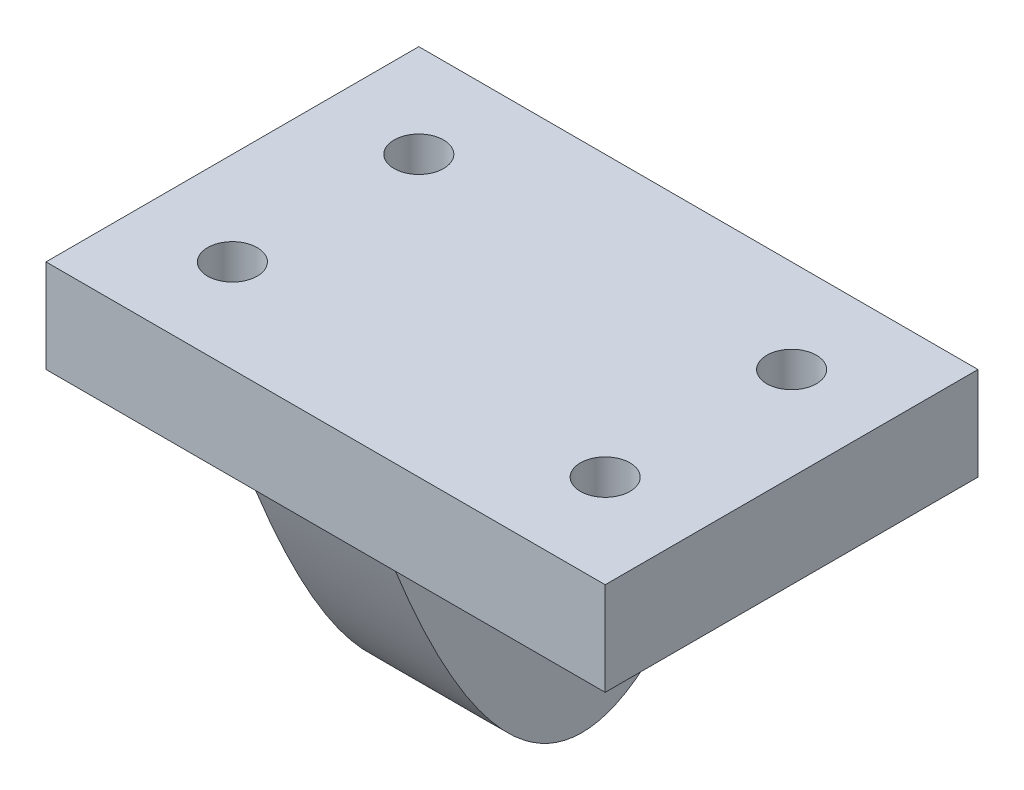
SolidWorks part; units mm, degrees
ref_plane "Front Plane" through (0, 0, 0) normal (0, 0, 1) x (1, 0, 0)
ref_plane "Top Plane" through (0, 0, 0) normal (0, 1, 0) x (1, 0, 0)
ref_plane "Right Plane" through (0, 0, 0) normal (1, 0, 0) x (0, 0, -1)
sketch "Sketch1" plane through (0, 0, 0) normal (0, 1, 0) x (1, 0, 0)
  line L0 (-38.1, 12.7) -> (38.1, 12.7) construction
  line L1 (-38.1, 25.4) -> (38.1, 25.4)
  line L2 (-38.1, 25.4) -> (-38.1, -25.4)
  line L3 (-38.1, -25.4) -> (38.1, -25.4)
  line L4 (38.1, 25.4) -> (38.1, -25.4)
  line L5 (-38.1, 25.4) -> (38.1, -25.4) construction
  line L6 (-38.1, -25.4) -> (38.1, 25.4) construction
  line L7 (-38.1, -12.7) -> (38.1, -12.7) construction
  line L8 (-25.4, 25.4) -> (-25.4, -25.4) construction
  line L9 (25.4, 25.4) -> (25.4, -25.4) construction
  line L10 (-9.525, 25.4) -> (-9.525, -25.4)
  line L11 (9.525, 25.4) -> (9.525, -25.4)
  circle A0 centre (-25.4, 12.7) radius 3.3782
  circle A1 centre (25.4, 12.7) radius 3.3782
  circle A2 centre (-25.4, -12.7) radius 3.3782
  circle A3 centre (25.4, -12.7) radius 3.3782
  point P0 (0, 0)
  dimension "D7" = 6.7564
  dimension "D1" = 76.2
  dimension "D2" = 50.8
  dimension "D3" = 25.4
  dimension "D4" = 12.7
  dimension "D5" = 12.7
  dimension "D6" = 12.7
  dimension "D8" = 28.575
  dimension "D9" = 28.575
extrude "Boss-Extrude1" add sketch "Sketch1" along normal blind 12.7 contours L10 L1 L2 L3 A2 A0 | L11 L1 L10 L3 | L1 L11 L3 L4 A3 A1 region at (-23.73, 0, 0) region at (0, 0, 0) region at (23.73, 0, 0)
extrude "Boss-Extrude2" add sketch "Sketch1<3>" against normal blind 44.45 contours L11 L1 L10 L3 region at (0, 0, 0)
sketch "Sketch1<3>" plane through (0, 0, 0) normal (0, 1, 0) x (1, 0, 0) same geometry as "Sketch1"
sketch "Sketch2" plane through (-9.525, 0, 0) normal (-1, 0, 0) x (0, 0, 1)
  line L0 (-25.4, -44.45) -> (25.4, -44.45) construction
  line L1 (0, 0) -> (0, -44.45) construction
  line L2 (-25.4, 0) -> (25.4, 0) construction
  circle A0 centre (0, -19.05) radius 3.3782
  spline S0 degree 2 poles (-25.4, 0) (0, -63.5) (25.4, 0) knots 0 0 0 1 1 1
  line M4 (-25.4, 0) -> (-25.4, -44.45)
  line M5 (-25.4, -44.45) -> (25.4, -44.45)
  line M6 (25.4, -44.45) -> (25.4, 0)
  dimension "D2" = 6.7564
  dimension "D1" = 25.4
  dimension "D3" = 12.7
extrude "Cut-Extrude1" cut sketch "Sketch2" against normal through all contours L1 S0 M4 M5 | S0 L1 M5 M6 | L1 A0 | A0 L1 region at (-9.525, -19.05, 1.4338) region at (-9.525, -30.8841, 15.5864) region at (-9.525, -30.8841, -15.5864) region at (-9.525, -19.05, -1.4338)
